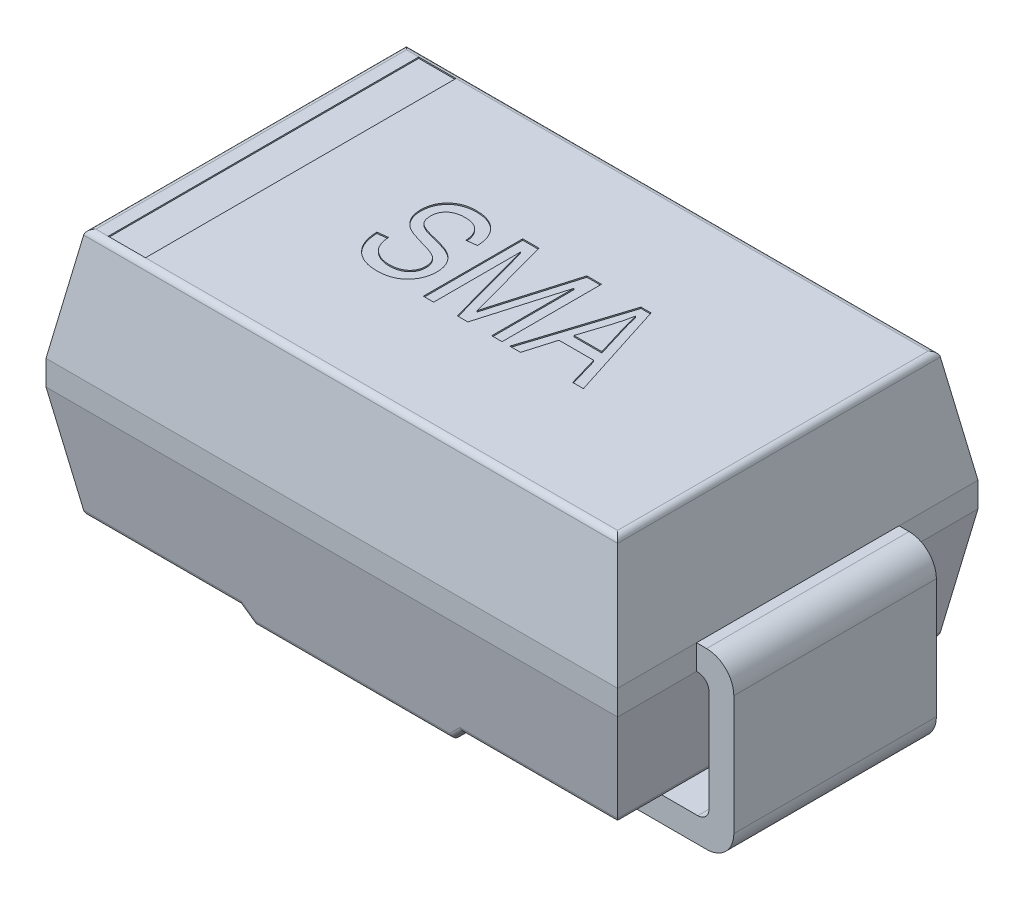
SolidWorks part; units mm, degrees
ref_plane "Спереди" through (0, 0, 0) normal (0, 0, 1) x (1, 0, 0)
ref_plane "Сверху" through (0, 0, 0) normal (0, 1, 0) x (1, 0, 0)
ref_plane "Справа" through (0, 0, 0) normal (1, 0, 0) x (0, 0, -1)
sketch "Эскиз1" plane through (0, 0, 0) normal (0, 0, 1) x (1, 0, 0)
  line L0 (-2.3, 2.1) -> (-2.3, 0.1)
  line L1 (-2.3, 0.1) -> (-0.9, 0.1)
  line L2 (-0.9, 0.1) -> (-0.8, 0)
  line L3 (-0.8, 0) -> (0.8, 0)
  line L4 (0.8, 0) -> (0.9, 0.1)
  line L5 (0.9, 0.1) -> (2.3, 0.1)
  line L6 (2.3, 0.1) -> (2.3, 2.1)
  line L7 (2.3, 2.1) -> (-2.3, 2.1)
  line L8 (0, -0.2601) -> (0, 2.3375) construction
  dimension "D1" = 0.1
  dimension "D2" = 2.1
  dimension "D3" = 1.8
  dimension "D4" = 4.6
extrude "Бобышка-Вытянуть1" add sketch "Эскиз1" along normal mid plane 2.9
sketch "Эскиз2" plane through (0, 0, 0) normal (0, 0, 1) x (1, 0, 0)
  line L0 (2.3, 1.2) -> (2.3807, 1.2)
  line L1 (2.3, 0.1) -> (2.3, 2.1) construction
  line L2 (2.6, 0.9807) -> (2.6, 0.0193)
  line L3 (2.3807, -0.2) -> (1.1, -0.2)
  line L4 (1.1, -0.2) -> (1.1, 0)
  line L5 (1.1, 0) -> (2.31, 0)
  line L6 (2.4, 0.09) -> (2.4, 0.91)
  line L7 (2.31, 1) -> (2.3, 1)
  line L8 (2.3, 1) -> (2.3, 1.2)
  line L9 (0.9, 0.1) -> (2.3, 0.1) construction
  line L10 (2.3, 1.1) -> (2.6721, 1.1) construction
  arc A0 (2.4, 0.91) -> (2.31, 1) centre (2.31, 0.91) ccw
  arc A1 (2.6, 0.9807) -> (2.3807, 1.2) centre (2.3807, 0.9807) ccw
  arc A2 (2.4, 0.09) -> (2.31, 0) centre (2.31, 0.09) cw
  arc A3 (2.6, 0.0193) -> (2.3807, -0.2) centre (2.3807, 0.0193) cw
  dimension "D8" = 0.09
  dimension "D9" = 0.1
  dimension "D10" = 0.09
  dimension "D11" = 0.1
  dimension "D1" = 0.2
  dimension "D2" = 0.1
  dimension "D3" = 0.1
  dimension "D4" = 0.2
  dimension "D5" = 1.5
  dimension "D6" = 0.1
  dimension "D7" = 0.1
extrude "Бобышка-Вытянуть2" add sketch "Эскиз2" along normal mid plane 1.63 separate body
mirror "Зеркальное отражение2" about plane through (0, 0, 0) normal (1, 0, 0) of "Бобышка-Вытянуть2"
chamfer "Фаска1" distance 0.9 angle 10 6 edges at (2.3, 2.1, 0) (2.3, 0.1, 0) (-2.3, 0.1, 0) (-2.3, 2.1, 0) (0, 2.1, -1.45) (0, 2.1, 1.45) first distance on face at (2.3, 1.1, 0) first distance on face at (-2.3, 1.1, 0) first distance on face at (0, 0.575, -1.45) first distance on face at (0, 0.575, 1.45)
chamfer "Фаска2" distance 1 angle 10 2 edges at (0, 0, -1.45) (0, 0, 1.45) first distance on face at (0, 0.48, -1.45) first distance on face at (0, 0.48, 1.45)
fillet "Скругление1" radius 0.05 16 edges at (0, 2.1, 1.2913) (-1.5207, 0.1, 1.2913) (1.5207, 0.1, 1.2913) (0.85, 0.05, 1.2825) (0, 0, 1.2737) (-0.85, 0.05, 1.2825) (-2.1413, 2.1, 0) (0, 2.1, -1.2913) (2.1413, 2.1, 0) (2.1413, 0.1, 0) (-2.1413, 0.1, 0) (1.5207, 0.1, -1.2913) (0.85, 0.05, -1.2825) (0, 0, -1.2737) (-0.85, 0.05, -1.2825) (-1.5207, 0.1, -1.2913)
sketch "Эскиз3" plane through (0, 2.1, 0) normal (0, 1, 0) x (1, 0, 0)
  line L0 (-2.0994, -1.2494) -> (2.0994, -1.2494) construction
  line L1 (2.0994, 1.2494) -> (-2.0994, 1.2494) construction
  line L2 (-2, 1.2494) -> (-1.7, 1.2494)
  line L3 (-2, 1.2494) -> (-2, -1.2494)
  line L4 (-2, -1.2494) -> (-1.7, -1.2494)
  line L5 (-1.7, 1.2494) -> (-1.7, -1.2494)
  line L6 (2.1486, -1.2986) -> (-2.1486, -1.2986) construction
  text T0 "SMA" font "Arial Narrow" height 0.8
  point P4 (0, -1.2494)
  point P10 (-1.7, 0)
  point P13 (0, -1.2986)
  dimension "D1" = 1
  dimension "D2" = 0.85
  dimension "D3" = 0.3
  dimension "D4" = 1.7
extrude "Вырез-Вытянуть1" cut sketch "Эскиз3" against normal blind 0.01
